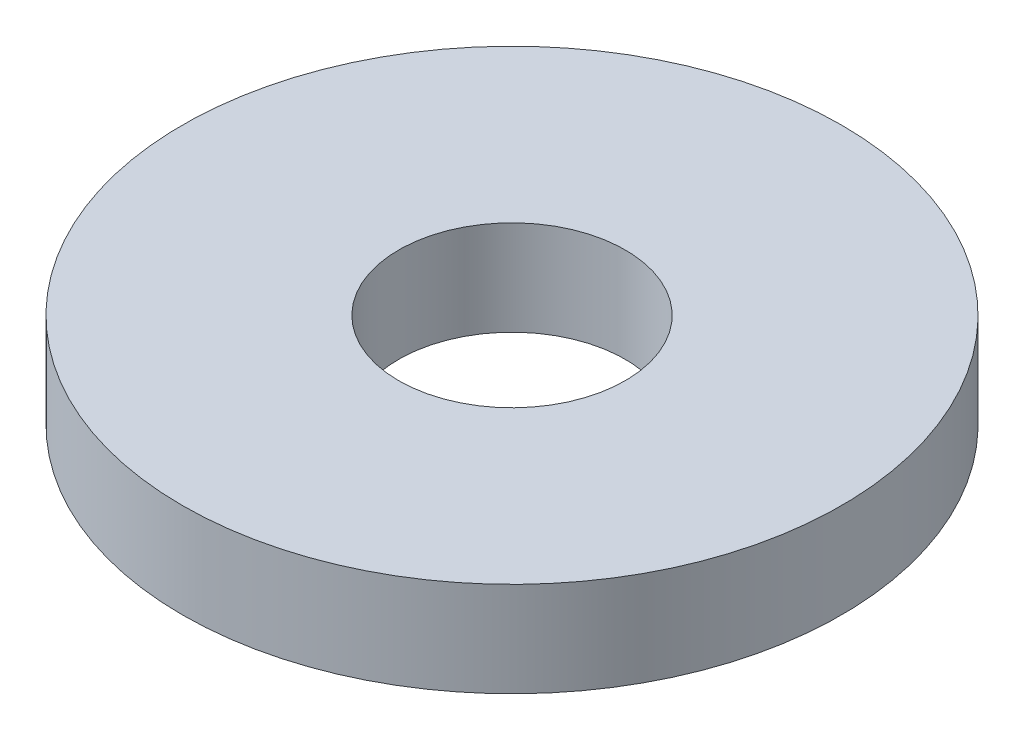
SolidWorks part; units mm, degrees
ref_plane "Front Plane" through (0, 0, 0) normal (0, 0, 1) x (1, 0, 0)
ref_plane "Top Plane" through (0, 0, 0) normal (0, 1, 0) x (1, 0, 0)
ref_plane "Right Plane" through (0, 0, 0) normal (1, 0, 0) x (0, 0, -1)
sketch "Sketch1" plane through (0, 0, 0) normal (0, 1, 0) x (1, 0, 0)
  circle A0 centre (0, 0) radius 80
  dimension "FLANGE_OD" = 160
extrude "Boss-Extrude1" add sketch "Sketch1" along normal blind 23
sketch "Sketch2" plane through (0, 0, 0) normal (0, 1, 0) x (1, 0, 0)
  circle A0 centre (0, 0) radius 27.5
  dimension "BORE_D" = 55
extrude "Cut-Extrude1" cut sketch "Sketch2" along normal through all
sketch "Sketch3" plane through (0, 23, 0) normal (0, 1, 0) x (1, 0, 0)
  circle A0 centre (0, 0) radius 18.5359 construction
  circle A1 centre (-18.5359, 0) radius 6.463
  dimension "BOLT_D" = 12.9261
  dimension "BOLT_PCD" = 37.0718
extrude "Cut-Extrude2" cut sketch "Sketch3" against normal blind 15.2833 rebuild error yes
pattern_circular "CirPattern1" count 6 over 360 rebuild error yes
